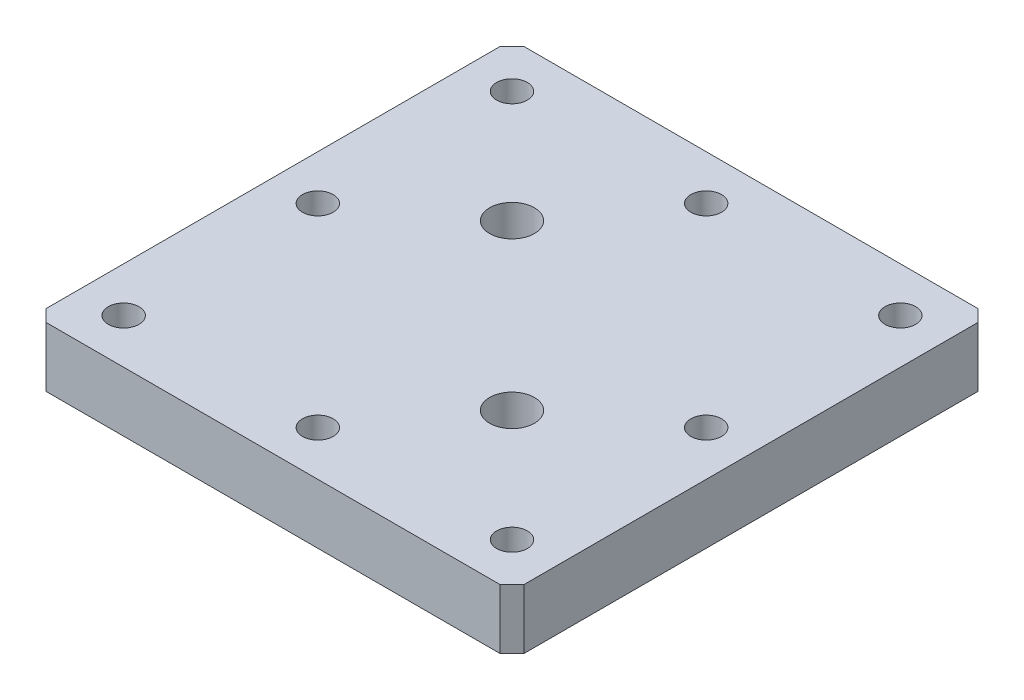
SolidWorks part; units mm, degrees
material "6061-T6 (SS)"
ref_plane "Front Plane" through (0, 0, 0) normal (0, 0, 1) x (1, 0, 0)
ref_plane "Top Plane" through (0, 0, 0) normal (0, 1, 0) x (1, 0, 0)
ref_plane "Right Plane" through (0, 0, 0) normal (1, 0, 0) x (0, 0, -1)
sketch "Sketch1" plane through (0, 0, 0) normal (0, 1, 0) x (1, 0, 0)
  line L0 (-50.8, 48.26) -> (-48.26, 50.8)
  line L1 (-48.26, -50.8) -> (48.26, -50.8)
  line L2 (-50.8, -48.26) -> (-50.8, 48.26)
  line L3 (-48.26, 50.8) -> (48.26, 50.8)
  line L4 (50.8, -48.26) -> (50.8, 48.26)
  line L5 (-50.8, -50.8) -> (50.8, 50.8) construction
  line L6 (-50.8, 50.8) -> (50.8, -50.8) construction
  line L7 (48.26, 50.8) -> (50.8, 48.26)
  line L8 (48.26, -50.8) -> (50.8, -48.26)
  line L9 (-50.8, -48.26) -> (-48.26, -50.8)
  line L10 (-41.275, 41.275) -> (0, 41.275)
  line L11 (41.275, -41.275) -> (-41.275, -41.275) construction
  line L12 (41.275, -41.275) -> (41.275, 41.275) construction
  line L13 (41.275, 41.275) -> (-41.275, 41.275) construction
  line L14 (-41.275, -41.275) -> (-41.275, 41.275) construction
  line L15 (41.275, -41.275) -> (-41.275, 41.275) construction
  line L16 (41.275, 41.275) -> (-41.275, -41.275) construction
  line L17 (41.275, -41.275) -> (0, -41.275)
  line L18 (-34.925, 34.925) -> (0, 0)
  line L19 (-34.925, -34.925) -> (34.925, -34.925)
  line L20 (-34.925, -34.925) -> (-34.925, 34.925)
  line L21 (-34.925, 34.925) -> (34.925, 34.925)
  line L22 (34.925, -34.925) -> (34.925, 34.925)
  line L23 (-34.925, -34.925) -> (34.925, 34.925) construction
  line L24 (-34.925, 34.925) -> (34.925, -34.925) construction
  line L25 (0, 0) -> (34.925, -34.925)
  circle A0 centre (-41.275, 41.275) radius 3.2639
  circle A1 centre (0, 41.275) radius 3.2639
  circle A2 centre (41.275, 41.275) radius 3.2639
  circle A3 centre (41.275, 0) radius 3.2639
  circle A4 centre (41.275, -41.275) radius 3.2639
  circle A5 centre (0, -41.275) radius 3.2639
  circle A6 centre (-41.275, -41.275) radius 3.2639
  circle A7 centre (-41.275, 0) radius 3.2639
  circle A8 centre (-20.6375, 41.275) radius 4.7625 construction
  circle A9 centre (20.6375, -41.275) radius 4.7625 construction
  circle A10 centre (-17.4625, 17.4625) radius 4.7625
  circle A11 centre (17.4625, -17.4625) radius 4.7625
  point P0 (0, 0)
  point P14 (0, 0)
  point P35 (0, 0)
  dimension "D5" = 6.5278
  dimension "D6" = 69.85
  dimension ".375" = 9.525
  dimension "D8" = 9.525
  dimension "D13" = 9.525
  dimension "D1" = 101.6
  dimension "D2" = 101.6
  dimension "D3" = 82.55
  dimension "D4" = 82.55
  dimension "D7" = 69.85
extrude "Boss-Extrude1" add sketch "Sketch1" along normal blind 12.7 contours L2 L9 L1 L8 L4 L7 L3 L0 A9 A4 A5 A8 A1 A0 A7 A6 A3 A2 L22 L19 L20 L21 | L20 L19 L22 L21 region at (-48.514, 0, -48.514)
extrude "Cut-Extrude5" cut sketch "Sketch1<4>" against normal through all and the other way through all contours L18 A10 | L18 A10 | L25 A11 | L25 A11 region at (-16.0332, 0, -18.8918) region at (-18.8918, 0, -16.0332) region at (16.0332, 0, 18.8918) region at (18.8918, 0, 16.0332)
sketch "Sketch1<4>" plane through (0, 0, 0) normal (0, 1, 0) x (1, 0, 0) same geometry as "Sketch1"
